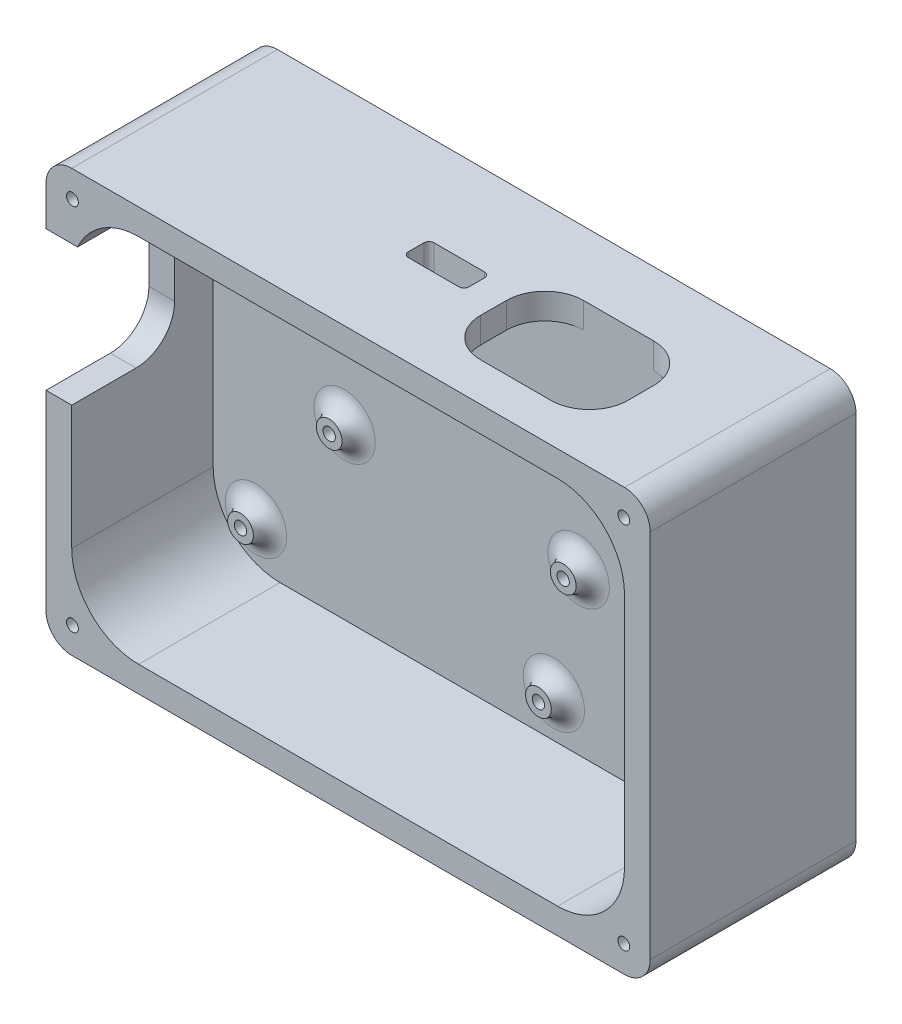
SolidWorks part; units mm, degrees
ref_plane "Front Plane" through (0, 0, 0) normal (0, 0, 1) x (1, 0, 0)
ref_plane "Top Plane" through (0, 0, 0) normal (0, 1, 0) x (1, 0, 0)
ref_plane "Right Plane" through (0, 0, 0) normal (1, 0, 0) x (0, 0, -1)
ref_plane "Plane1" through (0, 0, 1267.0007) normal (0, 0, -1) x (-1, 0, 0)
sketch "Sketch1" plane through (0, 0, 1267.0007) normal (0, 0, -1) x (-1, 0, 0)
  line L0 (-695.5296, 837.4474) -> (-695.5296, 897.8994) construction
  line L1 (-700.5296, 903.6614) -> (-593.0698, 903.6614)
  line L2 (-700.5296, 903.6614) -> (-700.5296, 831.66)
  line L3 (-700.5296, 831.66) -> (-593.0698, 831.66)
  line L4 (-593.0698, 903.6614) -> (-593.0698, 831.66)
  line L5 (-694.7676, 898.6614) -> (-598.8318, 898.6614) construction
  line L6 (-598.0698, 897.8994) -> (-598.0698, 837.4474) construction
  dimension "D1" = 5
  dimension "D2" = 5
  dimension "D3" = 5
  dimension "D4" = 5
extrude "Boss-Extrude1" add sketch "Sketch1" along normal blind 5
sketch "Sketch2" plane through (0, 0, 1267.0007) normal (0, 0, 1) x (1, 0, 0)
  circle A0 centre (692.0598, 895.8747) radius 2.5
  circle A1 centre (601.3798, 839.9968) radius 2.5
  circle A2 centre (692.0598, 862.8547) radius 2.5
  circle A3 centre (664.1198, 862.8547) radius 2.5
  circle A4 centre (602.0195, 895.2324) radius 2.5
  circle A5 centre (618.6145, 864.4774) radius 2.5
  circle A6 centre (659.2965, 839.6699) radius 2.5
  dimension "D1" = 5
extrude "Boss-Extrude2" add sketch "Sketch2" along normal up to surface (3 mm away)
fillet "Fillet1" radius 3.5 7 edges at (689.5598, 895.8747, 1267.0007) (689.5598, 862.8547, 1267.0007) (661.6198, 862.8547, 1267.0007) (616.1145, 864.4774, 1267.0007) (656.7965, 839.6699, 1267.0007) (599.5195, 895.2324, 1267.0007) (598.8798, 839.9968, 1267.0007)
sketch "Sketch3" plane through (0, 0, 1267.0007) normal (0, 0, 1) x (1, 0, 0)
  line L0 (700.5296, 903.6614) -> (700.5296, 831.66) construction
  line L1 (694.5296, 837.66) -> (684.5296, 837.66)
  line L2 (694.5296, 837.66) -> (694.5296, 855.66)
  line L3 (694.5296, 855.66) -> (684.5296, 855.66)
  line L4 (684.5296, 837.66) -> (684.5296, 855.66)
  line L5 (700.5296, 831.66) -> (593.0698, 831.66) construction
  dimension "D1" = 6
  dimension "D2" = 6
  dimension "D3" = 10
  dimension "D4" = 18
extrude "Cut-Extrude1" cut sketch "Sketch3" against normal through all
sketch "Sketch4" plane through (0, 0, 1262.0007) normal (0, 0, -1) x (-1, 0, 0)
  line L0 (-593.0698, 903.6614) -> (-700.5296, 903.6614) construction
  line L1 (-700.5296, 903.6614) -> (-593.0698, 903.6614)
  line L2 (-700.5296, 903.6614) -> (-700.5296, 831.66)
  line L3 (-700.5296, 831.66) -> (-593.0698, 831.66)
  line L4 (-593.0698, 903.6614) -> (-593.0698, 831.66)
  line L5 (-705.5296, 908.6614) -> (-588.0698, 908.6614)
  line L6 (-705.5296, 908.6614) -> (-705.5296, 826.66)
  line L7 (-705.5296, 826.66) -> (-588.0698, 826.66)
  line L8 (-588.0698, 908.6614) -> (-588.0698, 826.66)
  dimension "D1" = 5
  dimension "D2" = 5
  dimension "D3" = 5
  dimension "D4" = 5
extrude "Boss-Extrude3" add sketch "Sketch4" against normal blind 32.5
fillet "Fillet2" radius 13 4 edges at (700.5296, 903.6614, 1280.7507) (593.0698, 903.6614, 1280.7507) (593.0698, 831.66, 1280.7507) (700.5296, 831.66, 1280.7507)
fillet "Fillet4" radius 5 4 edges at (588.0698, 826.66, 1278.2507) (705.5296, 826.66, 1278.2507) (588.0698, 908.6614, 1278.2507) (705.5296, 908.6614, 1278.2507)
sketch "Sketch5" plane through (588.0698, 0, 0) normal (-1, 0, 0) x (0, 0, 1)
  line L0 (1262.0007, 831.66) -> (1262.0007, 903.6614) construction
  line L1 (1274.5007, 895.9849) -> (1294.5007, 895.9849)
  line L2 (1274.5007, 895.9849) -> (1274.5007, 868.7849)
  line L3 (1274.5007, 868.7849) -> (1294.5007, 868.7849)
  line L4 (1294.5007, 895.9849) -> (1294.5007, 868.7849)
  line L5 (1294.5007, 831.66) -> (1294.5007, 903.6614) construction
  dimension "D1" = 10
  dimension "D2" = 10
  dimension "D3" = 12.5
extrude "Cut-Extrude2" cut sketch "Sketch5" against normal up to next
sketch "Sketch6" plane through (0, 908.6614, 0) normal (0, 1, 0) x (1, 0, 0)
  line L1 (686.2098, -1287.0007) -> (657.5698, -1287.0007)
  line L2 (686.2098, -1287.0007) -> (686.2098, -1267.0007)
  line L3 (686.2098, -1267.0007) -> (657.5698, -1267.0007)
  line L4 (657.5698, -1287.0007) -> (657.5698, -1267.0007)
  line L5 (593.0698, -1262.0007) -> (700.5296, -1262.0007) construction
  line L6 (593.0698, -1294.5007) -> (700.5296, -1294.5007) construction
  dimension "D1" = 10
  dimension "D2" = 10
  dimension "D3" = 5
  dimension "D4" = 7.5
extrude "Cut-Extrude3" cut sketch "Sketch6" against normal up to next
sketch "Sketch7" plane through (0, 903.6614, 0) normal (0, -1, 0) x (1, 0, 0)
  line L0 (651.9672, 1271.8248) -> (648.9707, 1271.8248) construction
  line L1 (639.8389, 1276.8248) -> (651.6366, 1276.8248)
  line L2 (639.8389, 1276.8248) -> (639.8389, 1271.8248)
  line L3 (639.8389, 1271.8248) -> (651.6366, 1271.8248)
  line L4 (651.6366, 1276.8248) -> (651.6366, 1271.8248)
  line L5 (633.3239, 1276.8248) -> (656.1839, 1276.8248) construction
  line L6 (651.6366, 1276.2718) -> (651.6366, 1271.7718) construction
extrude "Cut-Extrude4" cut sketch "Sketch7" against normal up to next
fillet "Fillet11" radius 7.5 6 edges at (591.1398, 895.9849, 1274.5007) (590.5698, 868.7849, 1274.5007) (657.5698, 906.1614, 1267.0007) (686.2098, 906.1614, 1267.0007) (657.5698, 906.1614, 1287.0007) (686.2098, 906.1614, 1287.0007)
sketch "Sketch8" plane through (0, 0, 1262.0007) normal (0, 0, -1) x (-1, 0, 0)
  line L0 (-680.5296, 888.66) -> (-694.5296, 855.66)
  line L1 (-680.5296, 888.66) -> (-615.5296, 888.66)
  line L2 (-680.5296, 888.66) -> (-680.5296, 846.66) construction
  line L3 (-680.5296, 846.66) -> (-615.5296, 846.66)
  line L4 (-615.5296, 888.66) -> (-615.5296, 846.66)
  line L5 (-694.5296, 855.66) -> (-694.5296, 837.66)
  line L6 (-694.5296, 837.66) -> (-684.5296, 837.66)
  line L7 (-684.5296, 837.66) -> (-680.5296, 846.66)
  line L8 (-700.5296, 826.66) -> (-593.0698, 826.66) construction
  line L9 (-705.5296, 903.6614) -> (-705.5296, 831.66) construction
  line L10 (-705.5296, 903.6614) -> (-705.5296, 831.66)
  line L11 (-700.5296, 826.66) -> (-593.0698, 826.66)
  line L12 (-588.0698, 831.66) -> (-588.0698, 903.6614)
  line L13 (-700.5296, 908.6614) -> (-593.0698, 908.6614)
  arc A0 (-700.5296, 908.6614) -> (-705.5296, 903.6614) centre (-700.5296, 903.6614) ccw
  arc A1 (-593.0698, 908.6614) -> (-588.0698, 903.6614) centre (-593.0698, 903.6614) cw
  arc A2 (-588.0698, 831.66) -> (-593.0698, 826.66) centre (-593.0698, 831.66) cw
  arc A3 (-705.5296, 831.66) -> (-700.5296, 826.66) centre (-700.5296, 831.66) ccw
  dimension "D1" = 42
  dimension "D2" = 65
  dimension "D3" = 20
  dimension "D4" = 25
extrude "Boss-Extrude4" add sketch "Sketch8" along normal blind 7.5
sketch "Sketch9" plane through (0, 0, 1294.5007) normal (0, 0, 1) x (1, 0, 0)
  line L0 (589.5342, 907.1969) -> (596.8774, 899.8538) construction
  line L1 (588.0698, 895.9849) -> (588.0698, 903.6614) construction
  line L2 (705.5296, 867.6607) -> (719.7043, 867.6607) construction
  line L3 (705.5296, 903.6614) -> (705.5296, 831.66) construction
  line L4 (646.7997, 826.66) -> (646.7997, 819.6754) construction
  line L5 (700.5296, 826.66) -> (593.0698, 826.66) construction
  arc A0 (593.0698, 908.6614) -> (588.0698, 903.6614) centre (593.0698, 903.6614) ccw construction
  arc A1 (606.0698, 903.6614) -> (594.2097, 895.9849) centre (606.0698, 890.6614) ccw construction
  point P18 (593.2058, 903.5254)
  point P19 (700.3935, 903.5254)
  point P20 (593.2058, 831.796)
  point P21 (700.3935, 831.796)
  dimension "D1" = 45
hole_wizard "M2.5 Clearance Hole1" positions "Sketch9" profile "Sketch11" hole size "M2.5" standard "ANSI Metric"
sketch "Sketch11" plane through (700.3935, 831.796, 1294.5007) normal (1, 0, 0) x (0, -1, 0)
  line L0 (0, 0) -> (0, 8.691)
  line L1 (0, 8.691) -> (1.15, 8)
  line L2 (1.15, 8) -> (1.15, 0)
  line L5 (1.15, 0) -> (0, 0)
  line L10 (0, 8.691) -> (-1.15, 8) construction
  line L11 (0, -6.35) -> (0, 107.95) construction
  dimension "Hole Dia." = 2.3
  dimension "Hole Depth" = 8
  dimension "Drill Angle" = 118
ref_plane "Plane2" through (0, 0, 1274.5007) normal (0, 0, 1) x (1, 0, 0)
mirror "Mirror1" about plane through (0, 0, 1274.5007) normal (0, 0, 1) of "M2.5 Clearance Hole1"
fillet "Fillet7" radius 10 1 edges at (680.5296, 846.66, 1258.2507)
fillet "Fillet9" radius 3 3 edges at (680.5296, 888.66, 1258.2507) (615.5296, 888.66, 1258.2507) (615.5296, 846.66, 1258.2507)
fillet "Fillet10" radius 1 4 edges at (651.6366, 906.1614, 1276.8248) (651.6366, 906.1614, 1271.8248) (639.8389, 906.1614, 1271.8248) (639.8389, 906.1614, 1276.8248)
sketch "Sketch12" plane through (0, 0, 1270.0007) normal (0, 0, 1) x (1, 0, 0)
  point P0 (601.3798, 839.9968)
  point P1 (659.2965, 839.6699)
  point P3 (692.0498, 862.8347)
  point P5 (664.1098, 862.8347)
  point P7 (692.0598, 895.8747)
  point P9 (618.6145, 864.4774)
hole_wizard "M2.5 Clearance Hole2" positions "Sketch12" profile "Sketch13" hole size "M2.5" standard "ANSI Metric"
sketch "Sketch13" plane through (601.3798, 839.9968, 1270.0007) normal (1, 0, 0) x (0, -1, 0)
  line L0 (0, 0) -> (0, 7.721)
  line L1 (0, 7.721) -> (1.2, 7)
  line L2 (1.2, 7) -> (1.2, 0)
  line L5 (1.2, 0) -> (0, 0)
  line L10 (0, 7.721) -> (-1.2, 7) construction
  line L11 (0, -6.35) -> (0, 107.95) construction
  dimension "Hole Dia." = 2.4
  dimension "Hole Depth" = 7
  dimension "Drill Angle" = 118
